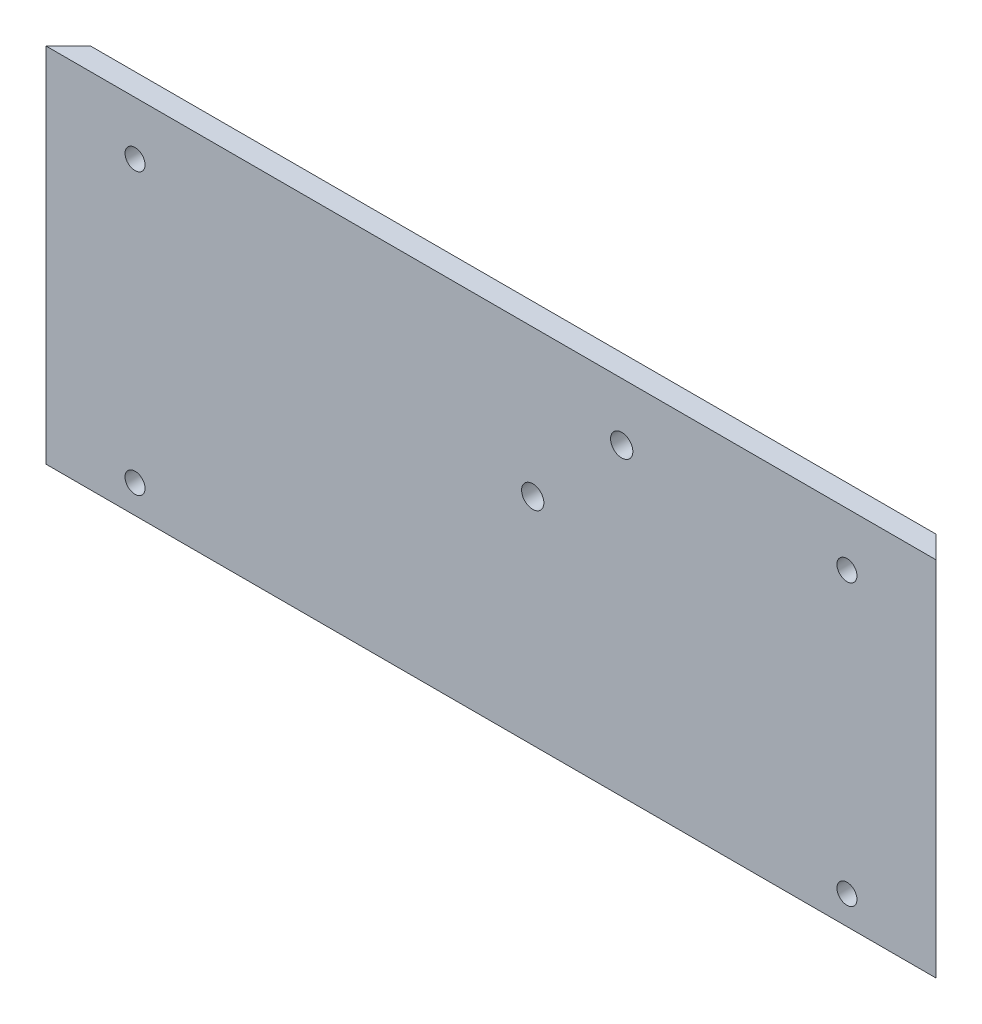
SolidWorks part; units mm, degrees
ref_plane "Front Plane" through (0, 0, 0) normal (0, 0, 1) x (1, 0, 0)
ref_plane "Top Plane" through (0, 0, 0) normal (0, 1, 0) x (1, 0, 0)
ref_plane "Right Plane" through (0, 0, 0) normal (1, 0, 0) x (0, 0, -1)
sketch "Sketch1" plane through (0, 0, 0) normal (0, 0, 1) x (1, 0, 0)
  line L0 (100, 84) -> (100, -37.3998) construction
  line L1 (0, 0) -> (200, 0)
  line L2 (0, 0) -> (0, 84)
  line L3 (0, 84) -> (200, 84)
  line L4 (200, 0) -> (200, 84)
  line L5 (0, 42) -> (200, 42) construction
  circle A0 centre (20, 9) radius 2.25
  circle A1 centre (180, 9) radius 2.25
  circle A4 centre (20, 72) radius 2.25
  circle A5 centre (180, 72) radius 2.25
  circle A6 centre (109.3775, 51) radius 2.5
  circle A7 centre (129.3775, 71) radius 2.5
  point P23 (109.8276, 42)
  dimension "D3" = 20
  dimension "D5" = 4.5
  dimension "D8" = 20
  dimension "D1" = 84
  dimension "D2" = 200
  dimension "D4" = 9
  dimension "D6" = 2
  dimension "D7" = 12
  dimension "D9" = 20
  dimension "D10" = 33
extrude "Boss-Extrude1" add sketch "Sketch1" against normal blind 5
sketch "Sketch2" plane through (0, 0, -5) normal (0, 0, -1) x (-1, 0, 0)
  line L0 (0, 0) -> (-200, 0) construction
  line L1 (0, 0) -> (-200, 0) construction
  line L2 (0, 5) -> (-200, 5)
  line L3 (-200, 5) -> (-200, 84)
  line L4 (-200, 84) -> (0, 84)
  line L5 (0, 84) -> (0, 5)
  circle A1 centre (-20, 9) radius 2.25 construction
  circle A2 centre (-180, 9) radius 2.25 construction
  circle A5 centre (-20, 9) radius 2.25
  circle A6 centre (-180, 9) radius 2.25
  circle A8 centre (-20, 72) radius 2.25 construction
  circle A9 centre (-180, 72) radius 2.25 construction
  circle A10 centre (-20, 72) radius 2.25
  circle A11 centre (-180, 72) radius 2.25
  dimension "D1" = 5
extrude "Boss-Extrude2" add sketch "Sketch2" along normal blind 3
chamfer "Chamfer1" distance 8 angle 45 3 edges at (200, 44.5, -8) (0, 44.5, -8) (100, 84, -8)
chamfer "Chamfer3" distance 3 angle 45 1 edges at (100, 84, -8)
sketch "Sketch3" plane through (100, 0, -100) normal (0.7071, 0, -0.7071) x (-0.7071, 0, -0.7071)
  line L0 (-141.4214, 0) -> (-141.4214, 2.6)
  line L1 (-141.4214, 0) -> (-141.4214, 84) construction
  line L2 (-141.4214, 2.6) -> (-134.3503, 2.6)
  line L4 (-134.3503, 2.6) -> (-134.3503, 0)
  line L5 (-134.3503, 0) -> (-141.4214, 0)
  line L6 (-130.1076, 5) -> (-134.3503, 5) construction
  dimension "D1" = 2.4
extrude "Cut-Extrude1" cut sketch "Sketch3" along direction (1, 0, 0) on the side against the normal through all
sketch "Sketch4" plane through (0, 0, 0) normal (0, 0, 1) x (1, 0, 0)
  circle A0 centre (109.3775, 51) radius 2.5 construction
  circle A1 centre (129.3775, 71) radius 2.5
  circle A2 centre (129.3775, 71) radius 2.5
  circle A3 centre (109.3775, 51) radius 2.5
  dimension "D1" = 0
extrude "Cut-Extrude2" cut sketch "Sketch4" against normal through all
